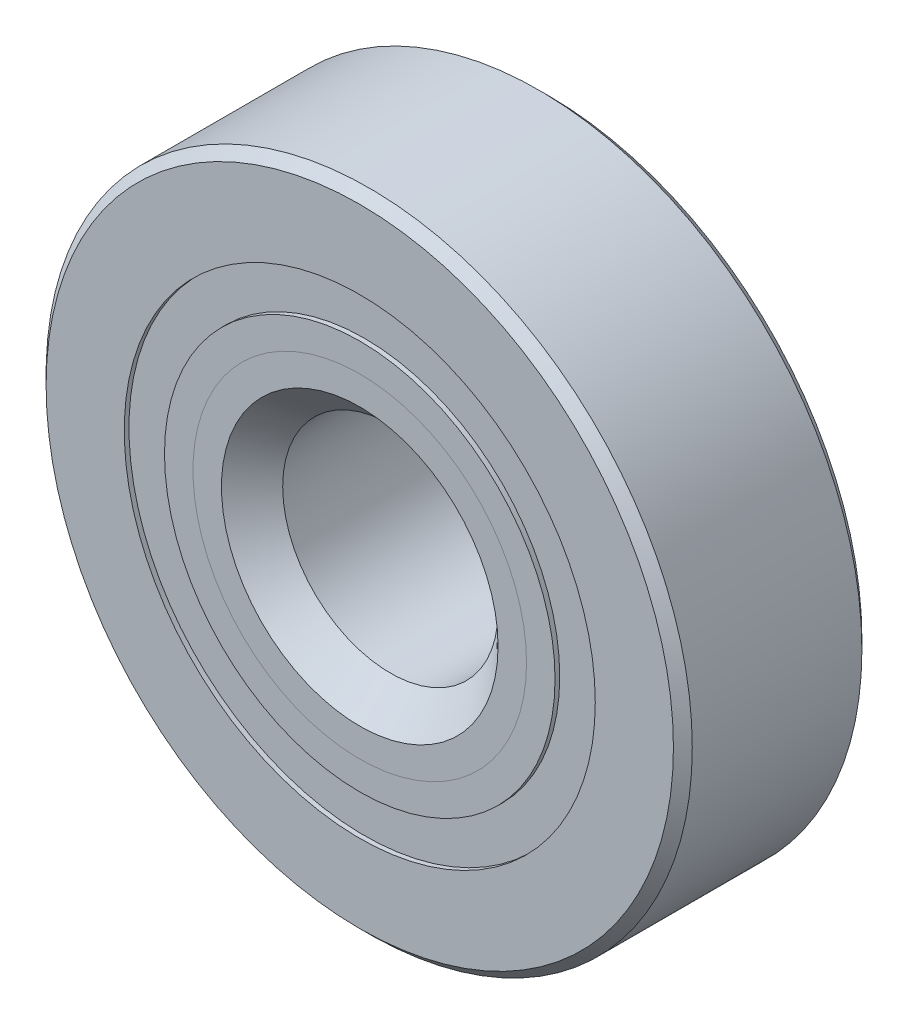
SolidWorks part; units mm, degrees
material "Alloy Steel"
ref_plane "Front Plane" through (0, 0, 0) normal (0, 0, 1) x (1, 0, 0)
ref_plane "Top Plane" through (0, 0, 0) normal (0, 1, 0) x (1, 0, 0)
ref_plane "Right Plane" through (0, 0, 0) normal (1, 0, 0) x (0, 0, -1)
sketch "Sketch1" plane through (0, 0, 0) normal (1, 0, 0) x (0, 0, -1)
  line L0 (-2.7781, 0) -> (2.7781, 0) construction
  line L1 (0, 9.525) -> (0, -9.525) construction
  line L2 (2.5003, 9.525) -> (-2.5003, 9.525)
  line L3 (-2.5003, 9.525) -> (-2.7781, 9.2472)
  line L4 (-2.7781, 9.2472) -> (-2.7781, 6.9431)
  line L5 (-2.7781, 6.9431) -> (-1.2347, 6.9431)
  line L6 (2.7781, 6.9431) -> (1.2347, 6.9431)
  line L7 (2.7781, 9.2472) -> (2.7781, 6.9431)
  line L8 (2.5003, 9.525) -> (2.7781, 9.2472)
  line L9 (0, 9.525) -> (0, 6.35) construction
  line L10 (0, 6.35) -> (0, 3.175) construction
  arc A0 (-1.2347, 6.9431) -> (1.2347, 6.9431) centre (0, 6.35) cw
  point P14 (0, 3.175)
  dimension "Width" = 5.5562
  dimension "OD" = 19.05
  dimension "D1" = 45
  dimension "D2" = 0.2778
  dimension "D3" = 2.4694
  dimension "D4" = 0.5931
revolve "Revolve1" add sketch "Sketch1" angle 360 about L0
sketch "Sketch2" plane through (0, 0, 0) normal (1, 0, 0) x (0, 0, -1)
  line L0 (-2.7781, 5.7569) -> (-1.2347, 5.7569)
  line L1 (-2.7781, 9.2472) -> (-2.7781, -9.2472) construction
  line L2 (-2.7781, 5.7569) -> (-2.7781, 4.9172)
  line L3 (-2.7781, 4.9172) -> (-1.9385, 4.0776)
  line L4 (-1.9385, 4.0776) -> (0, 4.0776)
  line L5 (0, 9.525) -> (0, -9.525) construction
  line L6 (0, 4.0776) -> (0, 4.9802)
  line L7 (0, 4.9802) -> (0, 3.175) construction
  line L8 (-2.7781, 5.7569) -> (-2.7781, 4.0776) construction
  line L9 (-2.7781, 4.0776) -> (-1.9385, 4.0776) construction
  arc A0 (-1.2347, 5.7569) -> (0, 4.9802) centre (0, 6.35) ccw
  arc A1 (1.2347, 6.9431) -> (-1.2347, 6.9431) centre (0, 6.35) ccw construction
  circle A2 centre (0, 6.35) radius 1.3698 construction
  dimension "D1" = 45
revolve "Revolve2" add sketch "Sketch2" angle 360 about L0
sketch "Sketch3" plane through (0, 0, 0) normal (1, 0, 0) x (0, 0, -1)
  line L0 (-2.7781, 4.9172) -> (-1.9385, 4.0776)
  line L1 (-1.9385, 4.0776) -> (0, 4.0776)
  line L2 (0, 4.0776) -> (0, 4.9802)
  line L3 (-2.7781, 4.9172) -> (-2.7781, 4.0776)
  line L4 (-2.7781, 5.7569) -> (-2.7781, 4.0776) construction
  line L5 (-2.7781, 4.0776) -> (-1.8755, 3.175)
  line L6 (-1.8755, 3.175) -> (2.5003, 3.175)
  line L7 (2.5003, 9.525) -> (2.5003, -9.525) construction
  line L8 (2.5003, 3.175) -> (2.7781, 3.4528)
  line L9 (2.7781, -9.2472) -> (2.7781, 9.2472) construction
  line L10 (2.7781, 3.4528) -> (2.7781, 5.7569)
  line L11 (2.7781, 5.7569) -> (1.2347, 5.7569)
  line L13 (2.5003, 9.525) -> (2.7781, 9.2472) construction
  circle A0 centre (0, 6.35) radius 1.3698 construction
  arc A1 (1.2347, 5.7569) -> (0, 4.9802) centre (0, 6.35) cw
revolve "Revolve3" add sketch "Sketch3" angle 360 about L0
sketch "Sketch4" plane through (0, 0, 0) normal (1, 0, 0) x (0, 0, -1)
  line L0 (-1.3698, 6.35) -> (1.3698, 6.35)
  circle A1 centre (0, 6.35) radius 1.3698 construction
  arc A2 (-1.3698, 6.35) -> (1.3698, 6.35) centre (0, 6.35) cw
  arc A3 (1.2347, 6.9431) -> (-1.2347, 6.9431) centre (0, 6.35) ccw construction
revolve "Revolve4" add sketch "Sketch4" angle 360 about L0
ref_axis "Axis1" through (0, 0, -2.7781) along (0, 0, 1)
pattern_circular "CirPattern1" count 10 every 36 about axis through (0, 0, -2.7781) along (0, 0, 1) of bodies 104
sketch "Sketch5" plane through (0, 0, 0) normal (1, 0, 0) x (0, 0, -1)
  line L0 (-2.7781, 6.9431) -> (-1.2347, 6.9431) construction
  line L1 (-2.6392, 6.9431) -> (-1.3698, 6.9431)
  line L2 (-2.6392, 6.9431) -> (-2.6392, 5.7569)
  line L3 (-2.6392, 5.7569) -> (-1.3698, 5.7569)
  line L4 (-1.3698, 6.9431) -> (-1.3698, 5.7569)
  line L5 (1.3698, 6.9431) -> (2.6392, 6.9431)
  line L6 (1.3698, 6.9431) -> (1.3698, 5.7569)
  line L7 (1.3698, 5.7569) -> (2.6392, 5.7569)
  line L8 (2.6392, 6.9431) -> (2.6392, 5.7569)
  line L9 (-2.7781, 5.7569) -> (-1.2347, 5.7569) construction
  line L10 (-2.6392, 9.3861) -> (-2.6392, 6.9431) construction
  line L11 (-2.5003, 9.525) -> (-2.7781, 9.2472) construction
  circle A0 centre (0, 6.35) radius 1.3698 construction
revolve "Revolve5" add sketch "Sketch5" angle 360 about L0
equation "\"D2@Sketch1\" = \"Width@Sketch1\"*.05"
equation "\"D3@Sketch1\" = \"Width@Sketch1\"/2.25"
equation "\"D4@Sketch1\" = (((\"OD@Sketch1\"-\"Width@Sketch1\")/2)/3.25)/3.5"
equation "\"D2@CirPattern1\" = 360/\"Balls@CirPattern1\""
